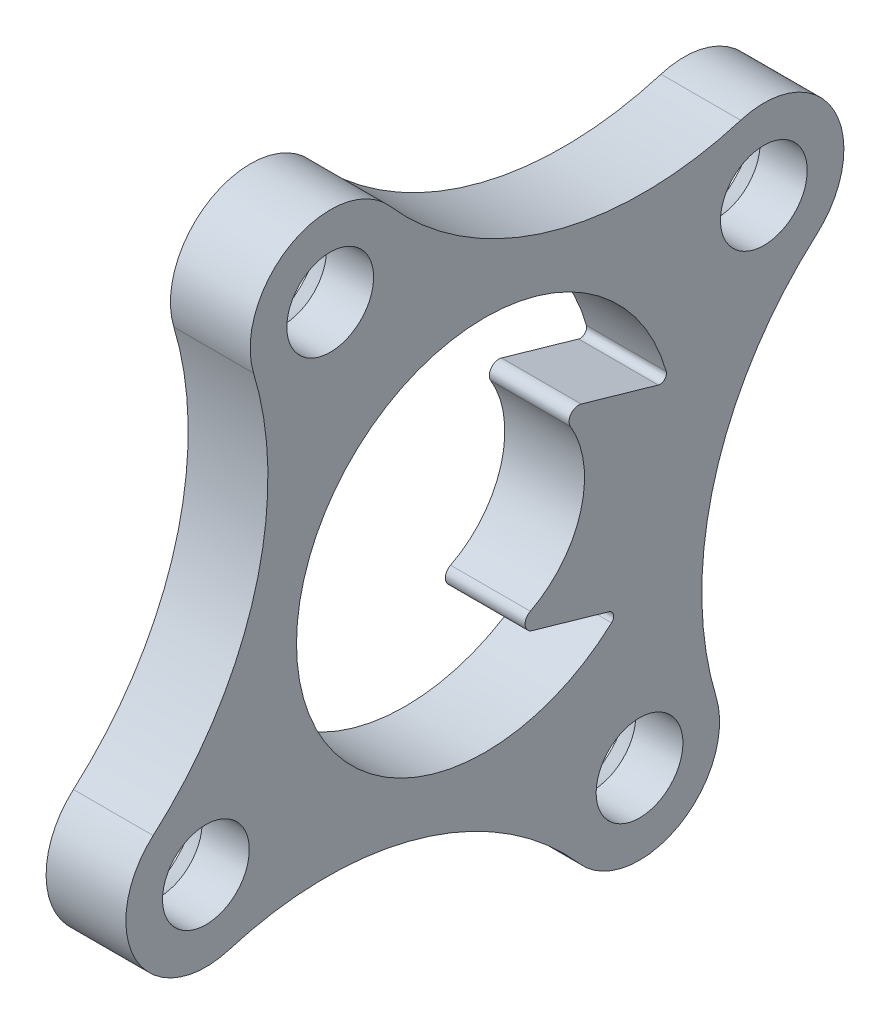
SolidWorks part; units mm, degrees
material "6061-T6 (SS)"
ref_plane "Front Plane" through (0, 0, 0) normal (0, 0, 1) x (1, 0, 0)
ref_plane "Top Plane" through (0, 0, 0) normal (0, 1, 0) x (1, 0, 0)
ref_plane "Right Plane" through (0, 0, 0) normal (1, 0, 0) x (0, 0, -1)
sketch "Sketch1" plane through (-52.0781, 0, 0) normal (-1, 0, 0) x (0, 0, 1)
  line L0 (-6.9048, 1.7195) -> (-3.8381, 2.5988)
  line L1 (-34.0142, 4.0065) -> (-35.1748, 4.0607) construction
  line L2 (-1.8779, -4.2377) -> (-4.9446, -5.117)
  line L3 (-4.7166, -5.3159) -> (-0.0181, -3.9687) construction
  line L5 (-37.0563, -3.3999) -> (-36.7386, -3.346) construction
  line L6 (6.1573, 11.1076) -> (-6.1573, -11.1076) construction
  line L7 (11.1076, -6.1573) -> (-11.1076, 6.1573) construction
  arc A0 (-3.8381, 2.5988) -> (-3.4061, 2.037) centre (-3.7331, 2.2326) cw
  arc A1 (-3.4061, 2.037) -> (-1.8092, -3.5324) centre (0, 0) ccw
  arc A2 (-1.8092, -3.5324) -> (-1.8779, -4.2377) centre (-1.9829, -3.8715) cw
  arc A3 (-0.0181, -3.9687) -> (-2.1183, 3.3561) centre (0, 0) ccw construction
  circle A4 centre (0, 0) radius 3.9687 construction
  arc A5 (-6.9048, 1.7195) -> (-7.2194, 2.0325) centre (-6.9749, 1.9636) cw
  arc A6 (9.2089, 10.1862) -> (3.7589, 13.2073) centre (6.1573, 11.1076) ccw construction
  arc A7 (9.2089, 10.1862) -> (13.2073, -3.7589) centre (22.0278, 6.316) ccw construction
  arc A8 (-7.2194, 2.0325) -> (-5.0455, -5.5491) centre (0, 0) cw
  arc A9 (-5.0455, -5.5491) -> (-4.9446, -5.117) centre (-4.8746, -5.3612) cw
  circle A12 centre (-11.1076, 6.1573) radius 3.175 construction
  circle A13 centre (-11.1076, 6.1573) radius 2.6924 construction
  circle A14 centre (0, 0) radius 9.525 construction
  arc A15 (10.1862, -9.2089) -> (13.2073, -3.7589) centre (11.1076, -6.1573) ccw construction
  arc A16 (10.1862, -9.2089) -> (-3.7589, -13.2073) centre (6.316, -22.0278) ccw construction
  arc A17 (-9.2089, -10.1862) -> (-3.7589, -13.2073) centre (-6.1573, -11.1076) ccw construction
  arc A18 (-9.2089, -10.1862) -> (-13.2073, 3.7589) centre (-22.0278, -6.316) ccw construction
  arc A19 (-10.1862, 9.2089) -> (-13.2073, 3.7589) centre (-11.1076, 6.1573) ccw construction
  arc A20 (-10.1862, 9.2089) -> (3.7589, 13.2073) centre (-6.316, 22.0278) ccw construction
  arc A21 (9.2089, 10.1862) -> (3.7589, 13.2073) centre (6.1573, 11.1076) ccw
  arc A22 (9.2089, 10.1862) -> (13.2073, -3.7589) centre (22.0278, 6.316) ccw
  arc A23 (10.1862, -9.2089) -> (13.2073, -3.7589) centre (11.1076, -6.1573) ccw
  arc A24 (10.1862, -9.2089) -> (-3.7589, -13.2073) centre (6.316, -22.0278) ccw
  arc A25 (-9.2089, -10.1862) -> (-3.7589, -13.2073) centre (-6.1573, -11.1076) ccw
  arc A26 (-9.2089, -10.1862) -> (-13.2073, 3.7589) centre (-22.0278, -6.316) ccw
  arc A27 (-10.1862, 9.2089) -> (-13.2073, 3.7589) centre (-11.1076, 6.1573) ccw
  arc A28 (-10.1862, 9.2089) -> (3.7589, 13.2073) centre (-6.316, 22.0278) ccw
  arc A29 (-4.8094, -5.7549) -> (-7.1282, 2.3321) centre (0, 0) ccw construction
  point P2 (0, 0)
  point P13 (-1.9815, 1.6795)
  point P15 (-0.7868, -0.4616)
  point P16 (29.3065, 8.8297)
  point P21 (36.8692, 4.7998)
  point P22 (36.0658, 5.0531)
  point P23 (0, 0)
  point P34 (0, 0)
  point P36 (0, -2.9434)
  dimension "D1" = 0.381
  dimension "D2" = 0.254
  dimension "D3" = 25.4
  dimension "D6" = 5.3848
  dimension "D7" = 19.05
  dimension "D5" = 45
  dimension "D8" = 7.112
extrude "Boss-Extrude1" add sketch "Sketch1" against normal blind 3.175
hole_wizard "CSK for #4 Flat Head Machine Screw1" positions "Sketch3" profile "Sketch4" countersink size "#4" standard "ANSI Inch" end condition up to next
sketch "Sketch3" plane through (-52.0781, 0, 0) normal (1, 0, 0) x (0, 0, -1)
  point P0 (11.1076, 6.1573)
  point P13 (-6.1573, 11.1076)
  point P16 (-11.1076, -6.1573)
  point P19 (6.1573, -11.1076)
sketch "Sketch4" plane through (-52.0781, 6.1573, -11.1076) normal (0, 1, 0) x (0, 0, 1)
  line L0 (0, 0) -> (0, 3.175)
  line L1 (0, 3.175) -> (1.7272, 3.175)
  line L2 (1.7272, 3.175) -> (1.7272, 1.3003)
  line L3 (1.7272, 1.3003) -> (2.8575, 0)
  line L5 (2.8575, 0) -> (0, 0)
  line L6 (-1.7272, 1.3003) -> (-2.8575, 0) construction
  line L11 (0, -6.35) -> (0, 107.95) construction
  dimension "Thru Hole Dia." = 3.4544
  dimension "Thru Hole Depth" = 3.175
  dimension "Near C'Sink Dia." = 5.715
  dimension "Near C'Sink Angle" = 82
